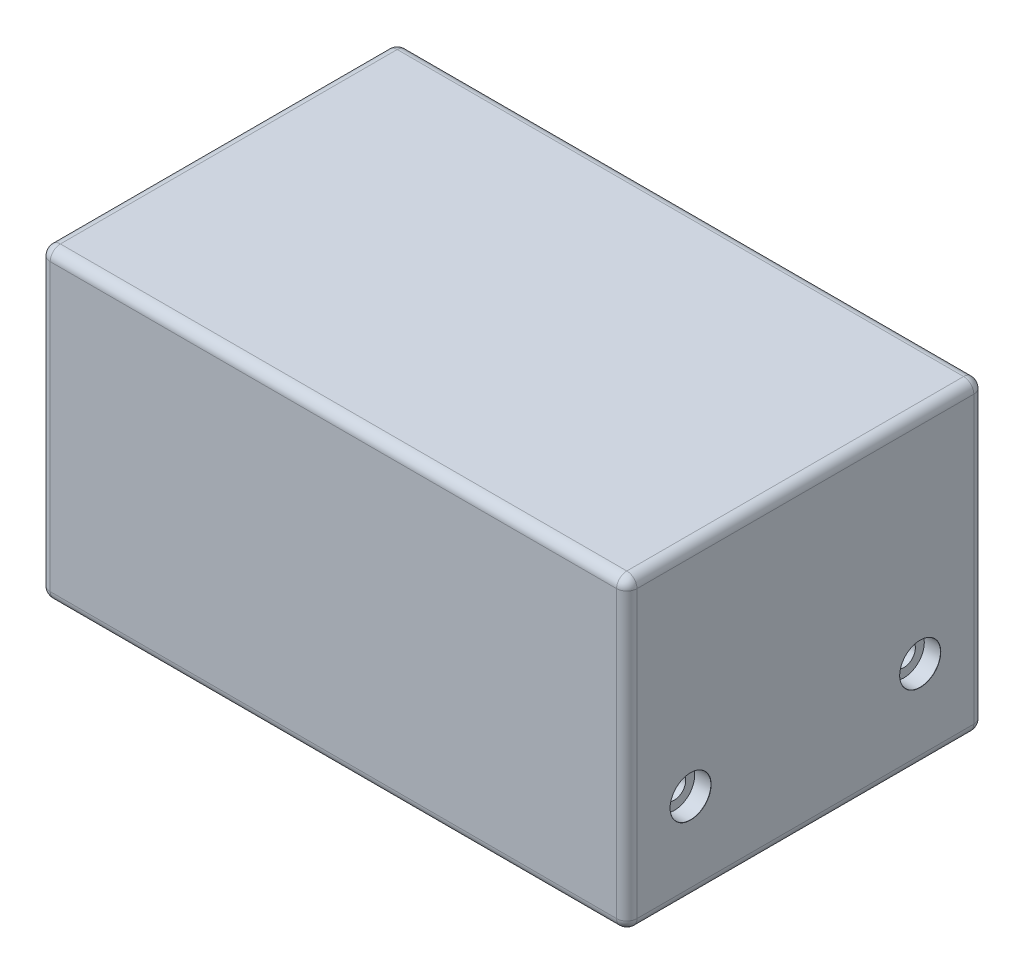
SolidWorks part; units mm, degrees
ref_plane "Alzado" through (0, 0, 0) normal (0, 0, 1) x (1, 0, 0)
ref_plane "Planta" through (0, 0, 0) normal (0, 1, 0) x (1, 0, 0)
ref_plane "Vista lateral" through (0, 0, 0) normal (1, 0, 0) x (0, 0, -1)
sketch "Croquis1" plane through (0, 0, 0) normal (0, 1, 0) x (1, 0, 0)
  line L1 (0, 0) -> (115, 0)
  line L2 (0, 0) -> (0, 70)
  line L3 (0, 70) -> (115, 70)
  line L4 (115, 0) -> (115, 70)
  dimension "D1" = 115
  dimension "D2" = 70
extrude "Saliente-Extruir1" add sketch "Croquis1" along normal blind 5
sketch "Croquis2" plane through (0, 5, 0) normal (0, 1, 0) x (1, 0, 0)
  line L0 (0, 0) -> (115, 0)
  line L1 (115, 0) -> (115, 70)
  line L2 (115, 70) -> (0, 70)
  line L3 (0, 70) -> (0, 65)
  line L4 (0, 70) -> (0, 0) construction
  line L5 (0, 65) -> (110, 65)
  line L6 (110, 65) -> (110, 5)
  line L7 (110, 5) -> (0, 5)
  line L8 (0, 5) -> (0, 0)
  dimension "D1" = 5
  dimension "D2" = 5
  dimension "D3" = 5
extrude "Saliente-Extruir2" add sketch "Croquis2" along normal blind 55
sketch "Croquis3" plane through (110, 0, 0) normal (-1, 0, 0) x (0, 0, 1)
  line L0 (-65, 60) -> (-65, 55)
  line L1 (-65, 60) -> (-65, 5) construction
  line L2 (-65, 55) -> (-5, 55)
  line L3 (-5, 60) -> (-5, 5) construction
  line L4 (-5, 55) -> (-5, 60)
  line L5 (-5, 60) -> (-65, 60)
  dimension "D1" = 5
extrude "Saliente-Extruir3" add sketch "Croquis3" along normal blind 110
sketch "Croquis4" plane through (110, 0, 0) normal (-1, 0, 0) x (0, 0, 1)
  line L0 (-65, 5) -> (-65, 10) construction
  line L1 (-65, 55) -> (-65, 5) construction
  line L2 (-5, 55) -> (-5, 5) construction
  line L3 (-65, 10) -> (-50, 10)
  line L4 (-65, 10) -> (-65, 25)
  line L5 (-65, 25) -> (-50, 25)
  line L6 (-50, 10) -> (-50, 25)
  line L7 (-5, 10) -> (-20, 10)
  line L8 (-5, 10) -> (-5, 25)
  line L9 (-5, 25) -> (-20, 25)
  line L10 (-20, 10) -> (-20, 25)
  line L11 (-65, 5) -> (-5, 5) construction
  dimension "D1" = 5
  dimension "D2" = 15
  dimension "D3" = 15
  dimension "D4" = 15
  dimension "D5" = 15
  dimension "D6" = 5
extrude "Saliente-Extruir4" add sketch "Croquis4" along normal blind 5
sketch "Croquis5" plane through (115, 0, 0) normal (1, 0, 0) x (0, 0, -1)
  line L0 (0, 0) -> (0, 17.5) construction
  line L1 (0, 60) -> (0, 0) construction
  line L2 (0, 17.5) -> (70, 17.5) construction
  line L3 (70, 60) -> (70, 0) construction
  line L4 (0, 17.5) -> (12.5, 17.5) construction
  point P5 (57.5, 17.5)
  point P10 (12.5, 17.5)
  dimension "D1" = 17.5
  dimension "D2" = 12.5
  dimension "D3" = 12.5
hole_wizard "Refrentado para tornillo con cabeza hueca de M41" positions "Croquis6" profile "Croquis7" counterbore size "M4" standard "DIN"
sketch "Croquis6" plane through (115, 0, 0) normal (1, 0, 0) x (0, 0, -1)
  point P0 (12.5, 17.5)
  point P3 (57.5, 17.5)
sketch "Croquis7" plane through (115, 17.5, -12.5) normal (0, 1, 0) x (0, 0, -1)
  line L0 (0, 0) -> (0, 21.8519)
  line L1 (0, 21.8519) -> (2.25, 20.5)
  line L2 (2.25, 20.5) -> (2.25, 3.2)
  line L3 (2.25, 3.2) -> (4, 3.2)
  line L5 (4, 3.2) -> (4, 0.025)
  line L6 (4, 0.025) -> (4.025, 0)
  line L7 (4.025, 0) -> (0, 0)
  line L8 (-4, 0.025) -> (-4.025, 0) construction
  line L10 (0, 21.8519) -> (-2.25, 20.5) construction
  line L11 (0, -6.35) -> (0, 107.95) construction
  dimension "Diámetro de taladro" = 4.5
  dimension "Profundidad de taladro" = 20.5
  dimension "Diámetro de refrentado" = 8
  dimension "Profundidad de refrentado" = 3.2
  dimension "Diámetro de avellanado cercano" = 8.05
  dimension "Ángulo de avellanado cercano" = 90
  dimension "Ángulo de perforador" = 118
fillet "Redondeo1" radius 2 12 edges at (57.5, 0, 0) (115, 0, -35) (0, 0, -35) (57.5, 0, -70) (115, 30, -70) (115, 60, -35) (115, 30, 0) (57.5, 60, 0) (0, 30, 0) (0, 60, -35) (0, 30, -70) (57.5, 60, -70)
